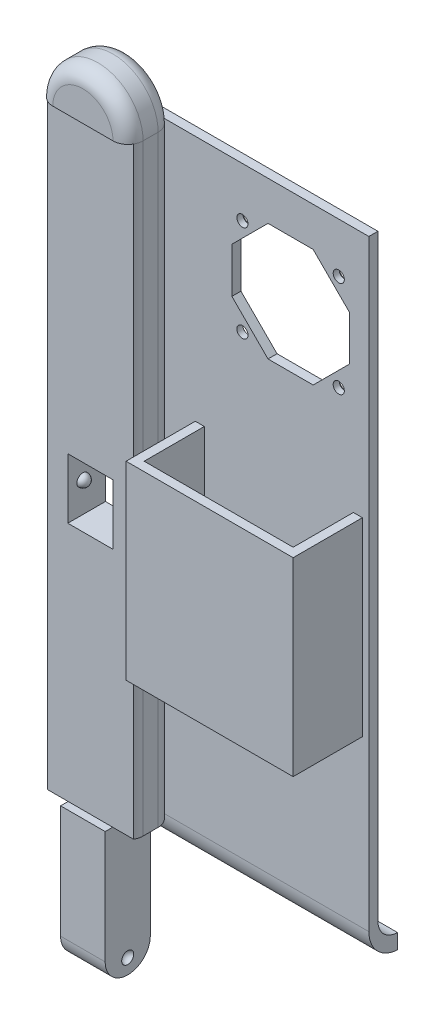
SolidWorks part; units mm, degrees
ref_plane "Front Plane" through (0, 0, 0) normal (0, 0, 1) x (1, 0, 0)
ref_plane "Top Plane" through (0, 0, 0) normal (0, 1, 0) x (1, 0, 0)
ref_plane "Right Plane" through (0, 0, 0) normal (1, 0, 0) x (0, 0, -1)
sketch "Sketch1" plane through (0, 0, 0) normal (0, 0, 1) x (1, 0, 0)
  line L0 (-7.4, -150) -> (7.4, -150)
  line L1 (7.4, -150) -> (7.4, -100)
  line L2 (7.4, -100) -> (15, -100)
  line L3 (15, -100) -> (15, 100)
  line L4 (-15, 100) -> (-15, -100)
  line L5 (-15, -100) -> (-7.4, -100)
  line L6 (-7.4, -100) -> (-7.4, -150)
  arc A0 (15, 100) -> (-15, 100) centre (0, 100) ccw
  point P7 (-15, 0)
  dimension "D2" = 14.8
  dimension "D3" = 15
  dimension "D1" = 250
  dimension "D4" = 15
  dimension "D5" = 50
extrude "Boss-Extrude1" add sketch "Sketch1" along normal mid plane 15
fillet "Fillet1" radius 5 8 edges at (15, 0, -7.5) (0, 115, -7.5) (15, 0, 7.5) (0, 115, 7.5) (-7.4, -150, 0) (7.4, -150, 0) (-15, 0, -7.5) (-15, 0, 7.5)
sketch "Sketch2" plane through (0, 0, 0) normal (0, 0, 1) x (1, 0, 0)
  line L0 (-23.2914, -140) -> (24.3018, -140) construction
  line L1 (-15, -100) -> (-10, -100) construction
  line L3 (-7.4, -100) -> (-7.4, -145) construction
  line L4 (-7.4, -138) -> (-7.4, -140)
  line L6 (7.4, -145) -> (7.4, -100) construction
  line L7 (7.4, -138) -> (7.4, -140)
  line L8 (-7.4, -140) -> (-5.4, -140)
  line L9 (7.4, -140) -> (5.4, -140)
  arc A2 (-5.4, -140) -> (-7.4, -138) centre (-7.4, -140) ccw
  arc A3 (5.4, -140) -> (7.4, -138) centre (7.4, -140) cw
  dimension "D1" = 40
  dimension "D2" = 2
  dimension "D3" = 2
sketch "Sketch3" plane through (0, 0, 0) normal (1, 0, 0) x (0, 0, -1)
  line L0 (7.5, -100) -> (7.5, 100) construction
  line L5 (17, -109.9875) -> (17, -104.9875)
  line L6 (10.5, -98.4875) -> (10.5, 100)
  line L7 (10.5, 100) -> (7.5, 100)
  line L8 (7.5, -100) -> (7.5, 100)
  arc A0 (7.5, -100) -> (17, -109.9875) centre (17.5, -100) ccw
  arc A1 (17, -104.9875) -> (10.5, -98.4875) centre (17, -98.4875) cw
  dimension "D1" = 10
  dimension "D4" = 6.5
  dimension "D2" = 3
  dimension "D3" = 5
sketch "Sketch4" plane through (0, 0, 7.5) normal (0, 0, 1) x (1, 0, 0)
  line L0 (-10, 100) -> (-10, -100) construction
  line L1 (-7.5, 0) -> (7.5, 0)
  line L2 (-7.5, 0) -> (-7.5, -20)
  line L3 (-7.5, -20) -> (7.5, -20)
  line L4 (7.5, 0) -> (7.5, -20)
  line L5 (-15, 100) -> (-10, 100) construction
  dimension "D1" = 20
  dimension "D2" = 15
  dimension "D3" = 2.5
extrude "Cut-Extrude1" cut sketch "Sketch4" against normal through all
sketch "Sketch5" plane through (0, 0, 0) normal (0, 0, 1) x (1, 0, 0)
  line L0 (-21.9659, -10) -> (20.5009, -10) construction
  line L1 (7.5, 0) -> (-7.5, 0) construction
  line L2 (-7.5, -10) -> (-5.5, -10)
  line L3 (-7.5, 0) -> (-7.5, -20) construction
  line L4 (-7.5, -8) -> (-7.5, -10)
  line L5 (7.5, -10) -> (5.5, -10)
  line L6 (7.5, -20) -> (7.5, 0) construction
  line L7 (7.5, -8) -> (7.5, -10)
  arc A0 (-5.5, -10) -> (-7.5, -8) centre (-7.5, -10) ccw
  arc A1 (5.5, -10) -> (7.5, -8) centre (7.5, -10) cw
  dimension "D1" = 10
  dimension "D2" = 2
  dimension "D3" = 2
revolve "Revolve2" add sketch "Sketch5" angle 360 about L0
revolve "Cut-Revolve1" cut sketch "Sketch2" angle 360 about L0
sketch "Sketch6" plane through (-7.4, 0, 0) normal (-1, 0, 0) x (0, 0, 1)
  line L0 (-7.5, -100) -> (-7.5, -145) construction
  line L1 (7.5, -100) -> (7.5, -145) construction
  line L2 (-7.5, -137.5) -> (-7.5, -150)
  line L3 (-7.5, -150) -> (7.5, -150)
  line L4 (7.5, -150) -> (-7.5, -150) construction
  line L5 (7.5, -150) -> (7.5, -137.5)
  line L6 (-7.5, -145) -> (7.5, -145) construction
  arc A0 (-7.5, -137.5) -> (7.5, -137.5) centre (0, -137.5) ccw
extrude "Cut-Extrude2" cut sketch "Sketch6" against normal through all
extrude "Boss-Extrude2" add sketch "Sketch3" along normal blind 80
sketch "Sketch7" plane through (0, 0, 0) normal (-1, 0, 0) x (0, 0, 1)
  line L0 (-10.5, 100) -> (-7.5, 100) construction
  line L1 (-7.5, 100) -> (-7.5, 0) construction
  line L2 (-7.5, 0) -> (-7.5, -20) construction
  line L3 (-7.5, -20) -> (-7.5, -100) construction
  line L4 (-17, -109.9875) -> (-17, -104.9875) construction
  line L5 (-10.5, -98.4875) -> (-10.5, 100) construction
  line L6 (-10.5, 100) -> (-7.5, 100)
  line L7 (-7.5, 100) -> (-7.5, 0)
  line L8 (-7.5, 0) -> (-7.5, -20)
  line L9 (-7.5, -20) -> (-7.5, -100)
  line L10 (-17, -109.9875) -> (-17, -104.9875)
  line L11 (-10.5, -98.4875) -> (-10.5, 100)
  arc A0 (-17, -109.9875) -> (-7.5, -100) centre (-17.5, -100) ccw construction
  arc A1 (-17, -104.9875) -> (-10.5, -98.4875) centre (-17, -98.4875) ccw construction
  arc A2 (-17, -109.9875) -> (-7.5, -100) centre (-17.5, -100) ccw
  arc A3 (-17, -104.9875) -> (-10.5, -98.4875) centre (-17, -98.4875) ccw
extrude "Boss-Extrude3" add sketch "Sketch7" along normal blind 5
sketch "Sketch9" plane through (0, 0, -10.5) normal (0, 0, -1) x (-1, 0, 0)
  line L0 (-7.5, -20) -> (-7.5, 0) construction
  line L1 (-7.5, -20) -> (-7.5, 0)
  line L2 (-7.5, 0) -> (5, 0) construction
  line L3 (5, -20) -> (-7.5, -20) construction
  line L4 (-7.5, 0) -> (5, 0)
  line L5 (5, -20) -> (-7.5, -20)
  line L6 (5, -20) -> (5, 0)
extrude "Cut-Extrude3" cut sketch "Sketch9" against normal blind 3
sketch "Sketch10" plane through (-15, 0, 0) normal (-1, 0, 0) x (0, 0, 1)
  line L0 (7.5, -100) -> (5, -100)
  line L1 (2.5, -100) -> (7.5, -100) construction
  line L2 (5, -100) -> (5, 100)
  line L3 (2.5, 100) -> (7.5, 100) construction
  line L4 (5, 100) -> (7.5, 100)
  line L5 (7.5, 100) -> (7.5, 110) construction
  line L6 (7.5, 100) -> (7.5, -100)
extrude "Cut-Extrude4" cut sketch "Sketch10" against normal through all
sketch "Sketch11" plane through (0, 0, -10.5) normal (0, 0, -1) x (-1, 0, 0)
  line L0 (-80, -98.4875) -> (5, -98.4875) construction
  line L1 (-46.5, 87.0125) -> (-61.5, 87.0125)
  line L2 (-61.5, 87.0125) -> (-73.5, 75.0125)
  line L3 (-73.5, 75.0125) -> (-73.5, 60.0125)
  line L4 (-73.5, 60.0125) -> (-61.5, 48.0125)
  line L5 (-61.5, 48.0125) -> (-46.5, 48.0125)
  line L6 (-46.5, 48.0125) -> (-34.5, 60.0125)
  line L7 (-34.5, 60.0125) -> (-34.5, 75.0125)
  line L8 (-34.5, 75.0125) -> (-46.5, 87.0125)
  line L9 (-80, -98.4875) -> (-80, 100) construction
  circle A1 centre (-38, 83.5125) radius 1.85
  circle A2 centre (-38, 51.5125) radius 1.85
  circle A3 centre (-70, 83.5125) radius 1.85
  circle A4 centre (-70, 51.5125) radius 1.85
  point P12 (-73.5, 67.5125)
  point P21 (-54, 87.0125)
  dimension "D1" = 32
  dimension "D8" = 3.7
  dimension "D9" = 16
  dimension "D2" = 32
  dimension "D3" = 32
  dimension "D4" = 150
  dimension "D5" = 39
  dimension "D6" = 15
  dimension "D7" = 39
  dimension "D10" = 10
  dimension "D11" = 16
extrude "Cut-Extrude5" cut sketch "Sketch11" against normal through all
sketch "Sketch12" plane through (0, 0, -10.5) normal (0, 0, -1) x (-1, 0, 0)
  circle A0 centre (-38, 83.5125) radius 3
  circle A1 centre (-70, 83.5125) radius 3
  circle A2 centre (-70, 51.5125) radius 3
  circle A3 centre (-38, 51.5125) radius 3.25
  dimension "D1" = 6
  dimension "D2" = 6
  dimension "D3" = 6
  dimension "D4" = 6.5
extrude "Cut-Extrude6" cut sketch "Sketch12" against normal blind 1
sketch "Sketch13" plane through (0, 100, 0) normal (0, 1, 0) x (1, 0, 0)
  line L0 (80, 7.5) -> (10, 7.5) construction
  line L2 (25.35, 7.5) -> (25.35, -12.5)
  line L3 (25.35, -12.5) -> (74.85, -12.5)
  line L4 (74.85, 7.5) -> (74.85, -12.5)
  line L5 (22.35, 7.5) -> (22.35, -15.5)
  line L6 (22.35, -15.5) -> (77.85, -15.5)
  line L7 (77.85, 7.5) -> (77.85, -15.5)
  line L9 (25.35, 7.5) -> (22.35, 7.5)
  line L10 (74.85, 7.5) -> (77.85, 7.5)
  line L11 (22.35, 10.5) -> (22.35, -15.5) construction
  line L12 (22.35, 10.5) -> (77.85, 10.5) construction
  line L13 (77.85, 10.5) -> (77.85, -15.5) construction
  line L14 (25.35, 7.5) -> (74.85, 7.5) construction
  dimension "D1" = 49.5
  dimension "D2" = 5.15
  dimension "D3" = 20
  dimension "D4" = 3
extrude "Boss-Extrude4" add sketch "Sketch13" against normal blind 170
sketch "Sketch14" plane through (77.85, 0, 0) normal (1, 0, 0) x (0, 0, -1)
  line L0 (7.5, 18.0125) -> (-15.5, 18.0125)
  line L1 (7.5, -70) -> (7.5, 100) construction
  line L2 (-15.5, -70) -> (-15.5, 100) construction
  line L3 (7.5, -41.9875) -> (-15.5, -41.9875)
  line L4 (-15.5, -41.9875) -> (-15.5, -70)
  line L5 (-15.5, -70) -> (7.5, -70)
  line L6 (7.5, -70) -> (7.5, -41.9875)
  line L7 (-15.5, 18.0125) -> (-15.5, 100)
  line L8 (-15.5, 100) -> (7.5, 100)
  line L9 (7.5, 100) -> (7.5, 18.0125)
  dimension "D1" = 30
  dimension "D2" = 60
extrude "Cut-Extrude7" cut sketch "Sketch14" against normal blind 56
sketch "Sketch15" plane through (77.85, 0, 0) normal (1, 0, 0) x (0, 0, -1)
  line L0 (7.5, 100) -> (7.5, -100) construction
  line L1 (-15.5, -41.9875) -> (7.5, -41.9875)
  line L2 (-15.5, -41.9875) -> (-15.5, -44.9875)
  line L3 (-15.5, -44.9875) -> (7.5, -44.9875)
  line L4 (7.5, -41.9875) -> (7.5, -44.9875)
  dimension "D1" = 3
extrude "Boss-Extrude5" add sketch "Sketch15" against normal blind 55.5
